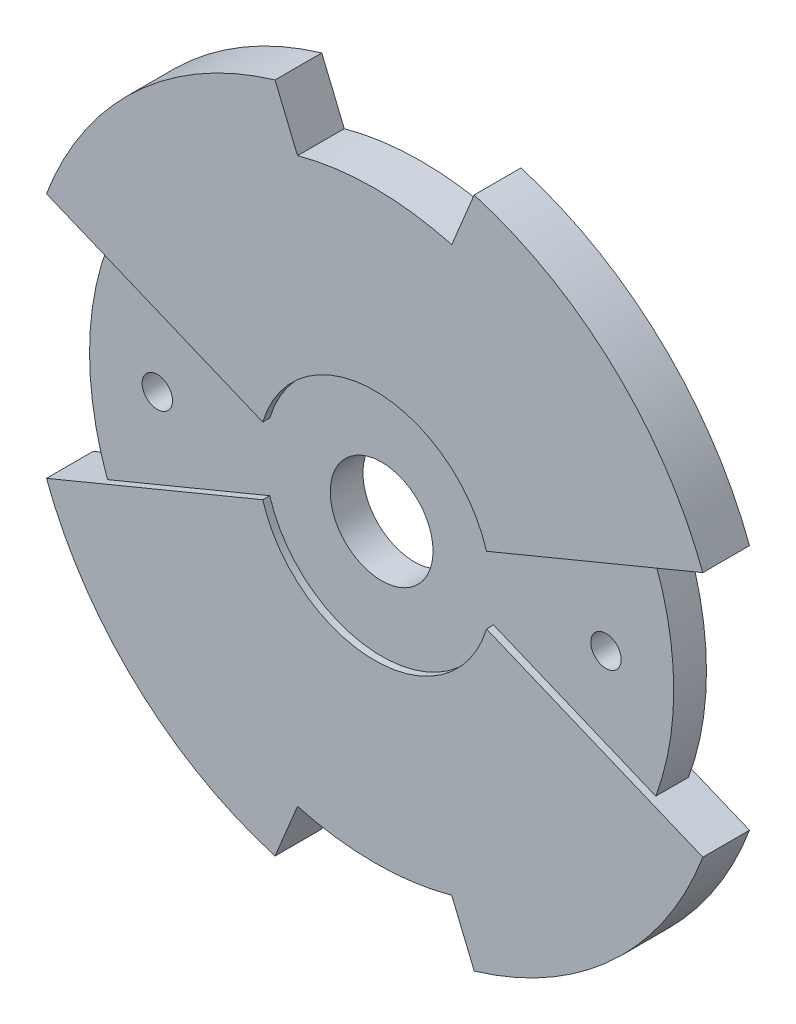
SolidWorks part; units mm, degrees
ref_plane "Front Plane" through (0, 0, 0) normal (0, 0, 1) x (1, 0, 0)
ref_plane "Top Plane" through (0, 0, 0) normal (0, 1, 0) x (1, 0, 0)
ref_plane "Right Plane" through (0, 0, 0) normal (1, 0, 0) x (0, 0, -1)
sketch "Sketch1" plane through (0, 0, 0) normal (0, 0, 1) x (1, 0, 0)
  line L0 (0, 0) -> (0, -50000) construction
  line L1 (0, 0) -> (-50000, 0) construction
  line L2 (23.9416, 7.1972) -> (70.2136, 26.3637)
  line L3 (23.9416, -7.1972) -> (70.2136, -26.3637)
  line L4 (-16.4954, 60.2839) -> (-21.3106, 71.9087)
  line L5 (16.4954, 60.2839) -> (21.3106, 71.9087)
  line L6 (16.4954, -60.2839) -> (21.3106, -71.9087)
  line L7 (-16.4954, -60.2839) -> (-21.3106, -71.9087)
  line L8 (-23.9416, -7.1972) -> (-70.2136, -26.3637)
  line L9 (-23.9416, 7.1972) -> (-70.2136, 26.3637)
  circle A0 centre (0, 0) radius 62.5
  arc A1 (70.2136, 26.3637) -> (21.3106, 71.9087) centre (0, 0) ccw
  arc A2 (23.9416, 7.1972) -> (-23.9416, 7.1972) centre (0, 0) ccw
  arc A3 (-21.3106, 71.9087) -> (-70.2136, 26.3637) centre (0, 0) ccw
  arc A4 (21.3106, -71.9087) -> (70.2136, -26.3637) centre (0, 0) ccw
  arc A5 (-70.2136, -26.3637) -> (-21.3106, -71.9087) centre (0, 0) ccw
  arc A6 (-23.9416, -7.1972) -> (23.9416, -7.1972) centre (0, 0) ccw
  point P15 (0, 0)
  point P16 (0, 0)
  dimension "D1" = 125
  dimension "D2" = 150
  dimension "D3" = 50
  dimension "D5" = 50.0845
  dimension "D4" = 45
  dimension "D6" = 45
  dimension "D7" = 12.5826
extrude "Boss-Extrude4" add sketch "Sketch1" along normal mid plane 10 contours A2 L2 A0 L9 | L2 A1 L5 A0 | L4 A3 L9 A0 | A6 L8 A0 L3 | L8 A5 L7 A0 | L6 A4 L3 A0 region at (0, 35.4405, 0) region at (45.115, 48.7493, 0) region at (-45.115, 48.7493, 0) region at (0, -35.4405, 0) region at (45.115, -48.7493, 0) region at (-45.115, -48.7493, 0)
extrude "Boss-Extrude5" add sketch "Sketch1<3>" along normal mid plane 7 contours L8 A6 L3 A0 L2 A2 L9 region at (0, 0, 0)
sketch "Sketch1<3>" plane through (0, 0, 0) normal (0, 0, 1) x (1, 0, 0) same geometry as "Sketch1"
sketch "Sketch2" plane through (0, 0, 3.5) normal (0, 0, 1) x (1, 0, 0)
  circle A0 centre (0, 0) radius 11
  circle A2 centre (0, 0) radius 48 construction
  circle A3 centre (48, 0) radius 3.25
  circle A4 centre (41.5692, -24) radius 3.25
  circle A5 centre (24, -41.5692) radius 3.25
  circle A6 centre (0, -48) radius 3.25
  circle A7 centre (-24, -41.5692) radius 3.25
  circle A8 centre (-41.5692, -24) radius 3.25
  circle A9 centre (-48, 0) radius 3.25
  circle A10 centre (-41.5692, 24) radius 3.25
  circle A11 centre (-24, 41.5692) radius 3.25
  circle A12 centre (0, 48) radius 3.25
  circle A13 centre (24, 41.5692) radius 3.25
  circle A14 centre (41.5692, 24) radius 3.25
  point P6 (0, 0)
  point P30 (0, 0)
  dimension "D1" = 22
  dimension "D2" = 96
  dimension "D3" = 6.5
  dimension "D4" = 12
extrude "Cut-Extrude3" cut sketch "Sketch2" against normal blind 10 contours A0
extrude "Cut-Extrude4" cut sketch "Sketch2<4>" against normal blind 25
sketch "Sketch2<4>" plane through (0, 0, 3.5) normal (0, 0, 1) x (1, 0, 0) same geometry as "Sketch2"
